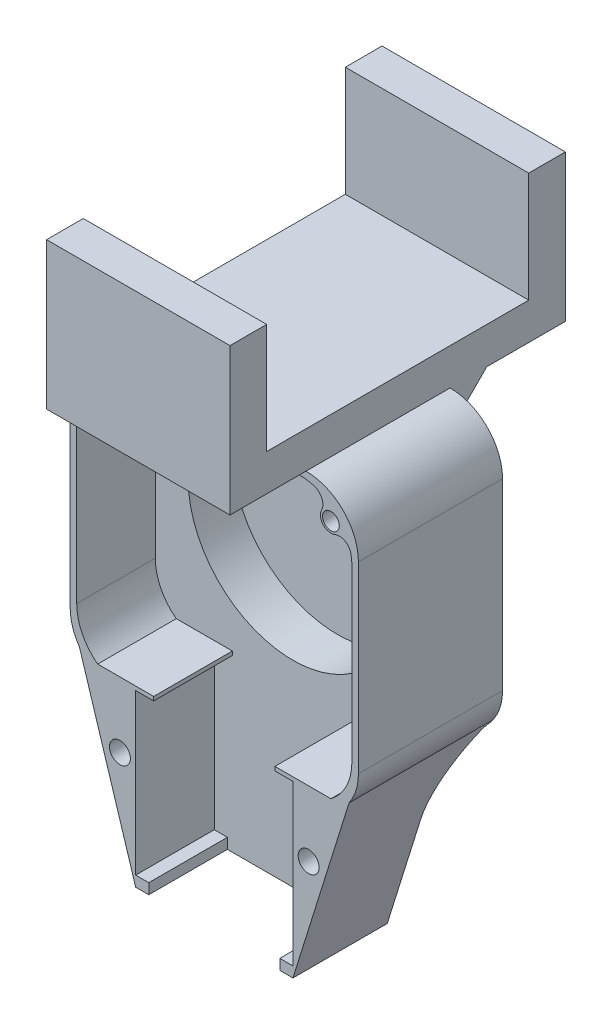
SolidWorks part; units mm, degrees
ref_plane "Alzado" through (0, 0, 0) normal (0, 0, 1) x (1, 0, 0)
ref_plane "Planta" through (0, 0, 0) normal (0, 1, 0) x (1, 0, 0)
ref_plane "Vista lateral" through (0, 0, 0) normal (1, 0, 0) x (0, 0, -1)
sketch "Croquis4" plane through (0, 0, 0) normal (0, 0, 1) x (1, 0, 0)
  line L9 (-17.5, 27.5) -> (17.5, 27.5)
  line L10 (-27.5, 17.5) -> (-27.5, -17.5)
  line L11 (-17.5, -27.5) -> (17.5, -27.5)
  line L12 (27.5, 17.5) -> (27.5, -17.5)
  line L13 (-27.5, 27.5) -> (27.5, -27.5) construction
  line L14 (-27.5, -27.5) -> (27.5, 27.5) construction
  circle A0 centre (0, 0) radius 2.5
  arc A1 (-27.5, -17.5) -> (-17.5, -27.5) centre (-17.5, -17.5) ccw
  arc A2 (17.5, -27.5) -> (27.5, -17.5) centre (17.5, -17.5) ccw
  arc A3 (17.5, 27.5) -> (27.5, 17.5) centre (17.5, 17.5) cw
  arc A4 (-17.5, 27.5) -> (-27.5, 17.5) centre (-17.5, 17.5) ccw
  point P0 (0, 0)
  dimension "D3" = 5
  dimension "D4" = 10
  dimension "D1" = 55
  dimension "D2" = 55
extrude "Saliente-Extruir1" add sketch "Croquis4" along normal blind 4
sketch "Croquis5" plane through (0, 0, 4) normal (0, 0, 1) x (1, 0, 0)
  line L1 (-17.5, 27.5) -> (17.5, 27.5)
  line L2 (-27.5, 17.5) -> (-27.5, -17.5)
  line L3 (-17.5, -27.5) -> (17.5, -27.5)
  line L4 (27.5, 17.5) -> (27.5, -17.5)
  line L5 (-27.5, 27.5) -> (27.5, -27.5) construction
  line L6 (-27.5, -27.5) -> (27.5, 27.5) construction
  circle A0 centre (0, 0) radius 20
  circle A1 centre (0, 0) radius 2.5 construction
  arc A2 (17.5, -27.5) -> (27.5, -17.5) centre (17.5, -17.5) ccw
  arc A3 (-27.5, -17.5) -> (-17.5, -27.5) centre (-17.5, -17.5) ccw
  arc A4 (17.5, 27.5) -> (27.5, 17.5) centre (17.5, 17.5) cw
  arc A5 (-17.5, 27.5) -> (-27.5, 17.5) centre (-17.5, 17.5) ccw
  point P4 (0, 0)
  dimension "D1" = 40
  dimension "D4" = 10
  dimension "D2" = 55
  dimension "D3" = 55
extrude "Saliente-Extruir2" add sketch "Croquis5" along normal blind 8.5
sketch "Croquis6" plane through (0, 0, 12.5) normal (0, 0, 1) x (1, 0, 0)
  line L1 (-25.7206, -23.194) -> (-15, -57.5)
  line L2 (-15, -57.5) -> (15, -57.5)
  line L3 (-17.5, -27.5) -> (17.5, -27.5) construction
  line L4 (15, -57.5) -> (25.7206, -23.194)
  line L8 (-17.5, -27.5) -> (17.5, -27.5)
  line L12 (25.119, -25.119) -> (27.5, -27.5) construction
  arc A1 (17.5, -27.5) -> (25.7206, -23.194) centre (17.5, -17.5) ccw
  arc A2 (-25.7206, -23.194) -> (-17.5, -27.5) centre (-17.5, -17.5) ccw
  point P5 (0, 0)
  dimension "D6" = 10
  dimension "D2" = 30
  dimension "D3" = 30
extrude "Saliente-Extruir4" add sketch "Croquis6" against normal blind 3
fillet "Redondeo1" radius 10 3 edges at (22.1401, -26.3583, 9.5) (-22.1401, -26.3583, 9.5) (0, -27.5, 9.5)
sketch "Croquis8" plane through (0, 0, 12.5) normal (0, 0, 1) x (1, 0, 0)
  line L0 (0, -57.5) -> (0, -20) construction
  line L1 (-15, -57.5) -> (15, -57.5) construction
  line L2 (-25.3906, -24.25) -> (-25.8417, -23.0151)
  line L3 (-15, -55.5) -> (-15, -25)
  line L4 (-17.5, 27.5) -> (17.5, 27.5)
  line L5 (12.5, -55.5) -> (15, -55.5)
  line L6 (-27.5, 17.5) -> (-27.5, -17.5)
  line L7 (-15, -25) -> (-11.5606, -25)
  line L8 (-11.5606, -25) -> (-11.5606, -24.25)
  line L9 (-11.5606, -24.25) -> (-25.3906, -24.25)
  line L10 (12.5, -57.5) -> (12.5, -55.5)
  line L11 (-25.7206, -23.194) -> (-15, -57.5) construction
  line L12 (-25.3906, -24.25) -> (-15, -57.5)
  line L13 (-15, -57.5) -> (-12.5, -57.5)
  line L14 (-12.5, -57.5) -> (-12.5, -55.5)
  line L15 (-12.5, -55.5) -> (-15, -55.5)
  line L16 (15, -57.5) -> (12.5, -57.5)
  line L17 (25.3906, -24.25) -> (15, -57.5)
  line L18 (11.5606, -24.25) -> (25.3906, -24.25)
  line L19 (11.5606, -25) -> (11.5606, -24.25)
  line L20 (15, -25) -> (11.5606, -25)
  line L21 (15, -55.5) -> (15, -25)
  line L23 (27.5, 17.5) -> (27.5, -17.5)
  line L24 (-27.5, 27.5) -> (27.5, -27.5) construction
  line L25 (-26.25, -26.25) -> (27.5, 27.5) construction
  line L26 (25.3906, -24.25) -> (25.862, -22.9843)
  line L28 (-16.25, 26.25) -> (16.25, 26.25)
  line L29 (-26.25, 16.25) -> (-26.25, -16.25)
  line L31 (26.25, 16.25) -> (26.25, -16.25)
  line L32 (-26.25, 26.25) -> (26.25, -26.25) construction
  line L33 (-26.25, -26.25) -> (26.25, 26.25) construction
  arc A9 (-27.5, -17.5) -> (-25.8417, -23.0151) centre (-17.5, -17.5) ccw
  arc A10 (25.862, -22.9843) -> (27.5, -17.5) centre (17.5, -17.5) ccw
  arc A11 (17.5, 27.5) -> (27.5, 17.5) centre (17.5, 17.5) cw
  arc A12 (-17.5, 27.5) -> (-27.5, 17.5) centre (-17.5, 17.5) ccw
  arc A13 (-26.25, -16.25) -> (-22.25, -24.25) centre (-16.25, -16.25) ccw
  arc A14 (22.25, -24.25) -> (26.25, -16.25) centre (16.25, -16.25) ccw
  arc A15 (16.25, 26.25) -> (19.0082, 25.8621) centre (16.25, 16.25) cw
  arc A16 (-16.25, 26.25) -> (-19.0082, 25.8621) centre (-16.25, 16.25) ccw
  arc A18 (-26.0816, 18.075) -> (-23.0104, 19.7822) centre (-23.865, 17.7034) cw
  arc A19 (-20.4641, 22.5324) -> (-19.0082, 25.8621) centre (-18.3575, 23.5944) cw
  arc A21 (-26.0727, 18.1248) -> (-26.25, 16.25) centre (-16.25, 16.25) ccw
  arc A22 (-23.0104, 19.7822) -> (-20.4641, 22.5324) centre (-22.25, 21.632) ccw
  arc A23 (26.0816, 18.075) -> (23.0104, 19.7822) centre (23.865, 17.7034) ccw
  arc A24 (20.4641, 22.5324) -> (19.0082, 25.8621) centre (18.3575, 23.5944) ccw
  arc A25 (23.0104, 19.7822) -> (20.4641, 22.5324) centre (22.25, 21.632) cw
  arc A26 (26.0727, 18.1248) -> (26.25, 16.25) centre (16.25, 16.25) cw
  circle A27 centre (-18, -36.75) radius 2
  circle A28 centre (18, -36.75) radius 2
  point P0 (0, 0)
  point P3 (0, 0)
  point P7 (0, -57.5)
  point P10 (0, 0)
  point P16 (0, -42.5)
  arc M7 (-27.5, -17.5) -> (-25.7206, -23.194) centre (-17.5, -17.5) ccw
  line M8 (-25.7206, -23.194) -> (-15, -57.5)
  line M9 (-15, -57.5) -> (15, -57.5)
  line M10 (15, -57.5) -> (25.7206, -23.194)
  arc M11 (25.7206, -23.194) -> (27.5, -17.5) centre (17.5, -17.5) ccw
  line M12 (27.5, -17.5) -> (27.5, 17.5)
  arc M13 (27.5, 17.5) -> (17.5, 27.5) centre (17.5, 17.5) ccw
  line M14 (17.5, 27.5) -> (-17.5, 27.5)
  arc M15 (-17.5, 27.5) -> (-27.5, 17.5) centre (-17.5, 17.5) ccw
  line M16 (-27.5, 17.5) -> (-27.5, -17.5)
  dimension "D3" = 55
  dimension "D4" = 55
  dimension "D7" = 52.5
  dimension "D9" = 10
  dimension "D10" = 12.5
  dimension "D5" = 10
  dimension "D6" = 52.5
  dimension "D8" = 15
  dimension "D11" = 90
  dimension "D12" = 3
  dimension "D13" = 4
  dimension "D14" = 32.5
  dimension "D20" = 0.75
  dimension "D21" = 90
  dimension "D22" = 90
  dimension "D23" = 2.5
  dimension "D24" = 2.5
  dimension "D25" = 2
extrude "Saliente-Extruir5" add sketch "Croquis8" along normal blind 15 contours A16 L28 A15 L31 A14 L18 L9 A13 L29 M10 M11 M12 M13 M14 M15 M16 M7 M8 | L14 L15 L3 L7 L8 L9 M8 M9 | L21 L5 L10 L18 L19 L20 M9 M10 region at (-24.8348, -23.4967, 12.5) region at (-23.8203, -24.6101, 12.5) region at (12.8601, -56.5, 12.5)
sketch "Croquis9" plane through (0, 0, 27.5) normal (0, 0, 1) x (1, 0, 0)
  line L0 (0, 23.4791) -> (0, 0) construction
  circle A0 centre (-22.25, 21.632) radius 1.6
  arc A1 (-23.0104, 19.7822) -> (-20.4641, 22.5324) centre (-22.25, 21.632) ccw construction
  circle A2 centre (-18, -36.75) radius 1.6
  circle A3 centre (-18, -36.75) radius 2 construction
  circle A4 centre (18, -36.75) radius 1.6
  circle A5 centre (22.25, 21.632) radius 1.6
  dimension "D1" = 3.2
  dimension "D2" = 3.2
extrude "Cortar-Extruir1" cut sketch "Croquis9" against normal through all
sketch "Croquis11" plane through (0, 27.5, 0) normal (0, 1, 0) x (1, 0, 0)
  line L0 (17.5, 0) -> (-17.5, 0) construction
  line L1 (-17.5, 15) -> (17.5, 15)
  line L2 (-17.5, 15) -> (-17.5, -35)
  line L3 (-17.5, -35) -> (17.5, -35)
  line L4 (17.5, 15) -> (17.5, -35)
  point P4 (0, 15)
  dimension "D1" = 50
  dimension "D2" = 35
  dimension "D3" = 15
extrude "Saliente-Extruir7" add sketch "Croquis11" along normal blind 7
sketch "Croquis12" plane through (0, 27.5, 0) normal (0, -1, 0) x (1, 0, 0)
  line L0 (-17.5, 35) -> (17.5, 35) construction
  line L1 (-17.5, 35) -> (17.5, 35)
  line L2 (-17.5, 35) -> (-17.5, 42)
  line L3 (-17.5, 42) -> (17.5, 42)
  line L4 (17.5, 35) -> (17.5, 42)
  line L5 (-17.5, -15) -> (17.5, -15)
  line L6 (-17.5, -15) -> (-17.5, -22)
  line L7 (-17.5, -22) -> (17.5, -22)
  line L8 (17.5, -15) -> (17.5, -22)
  line L9 (17.5, -15) -> (-17.5, -15) construction
  dimension "D1" = 7
  dimension "D2" = 7
  dimension "D3" = 35
  dimension "D4" = 35
extrude "Saliente-Extruir8" add sketch "Croquis12" against normal blind 28
chamfer "Chaflán2" distance 7 angle 45 1 edges at (0, 27.5, 0)
sketch "Croquis13" plane through (0, 0, 0) normal (0, 0, -1) x (-1, 0, 0)
  circle A0 centre (0, 0) radius 11.05
  dimension "D1" = 22.1
extrude "Cortar-Extruir2" cut sketch "Croquis13" against normal blind 2
